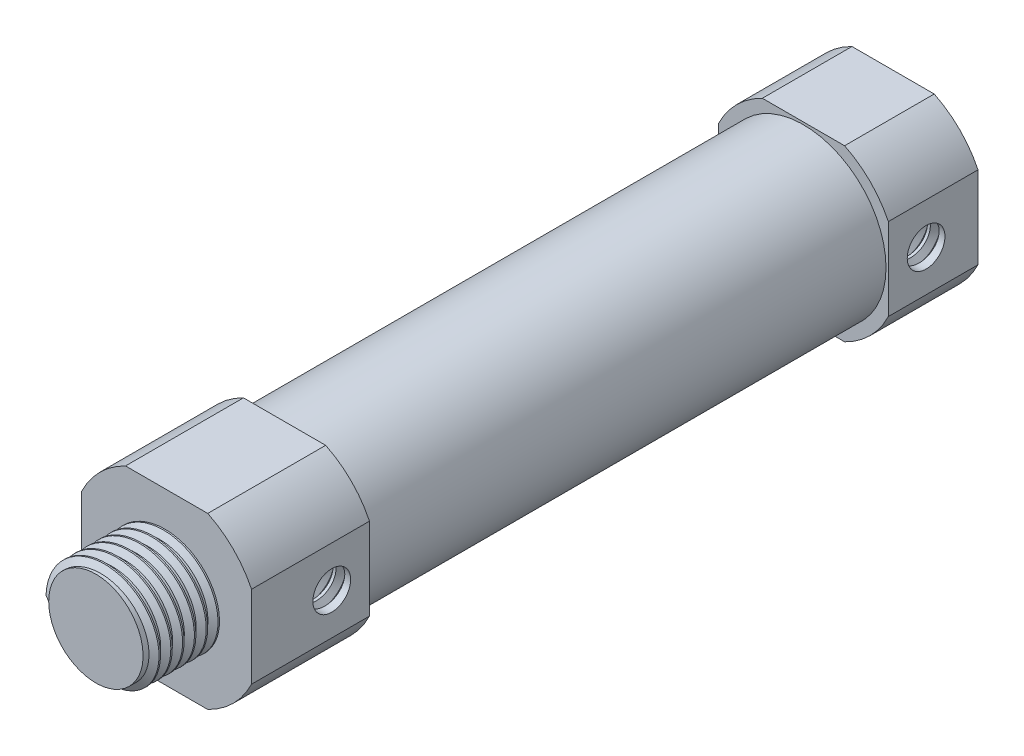
SolidWorks part; units mm, degrees
material "1060 合金"
ref_plane "前视基准面" through (0, 0, 0) normal (0, 0, 1) x (1, 0, 0)
ref_plane "上视基准面" through (0, 0, 0) normal (0, 1, 0) x (1, 0, 0)
ref_plane "右视基准面" through (0, 0, 0) normal (1, 0, 0) x (0, 0, -1)
sketch "草图1" plane through (0, 0, 0) normal (0, 0, 1) x (1, 0, 0)
  circle A0 centre (0, 0) radius 10
  dimension "D1" = 20
extrude "凸台-拉伸1" add sketch "草图1" along normal blind 9.5
sketch "草图2" plane through (0, 0, 9.5) normal (0, 0, 1) x (1, 0, 0)
  line L1 (-9, 9) -> (9, 9)
  line L2 (-9, 9) -> (-9, -9)
  line L3 (-9, -9) -> (9, -9)
  line L4 (9, 9) -> (9, -9)
  line L5 (-9, 9) -> (9, -9) construction
  line L6 (-9, -9) -> (9, 9) construction
  circle A0 centre (0, 0) radius 15
  point P0 (0, 0)
  dimension "D2" = 30
  dimension "D1" = 18
extrude "切除-拉伸1" cut sketch "草图2" against normal blind 9.5
sketch "草图3" plane through (0, 0, 9.5) normal (0, 0, 1) x (1, 0, 0)
  circle A0 centre (0, 0) radius 8.75
  dimension "D1" = 17.5
extrude "凸台-拉伸2" add sketch "草图3" along normal blind 55
sketch "草图4" plane through (0, 0, 64.5) normal (0, 0, 1) x (1, 0, 0)
  line L1 (9, -9) -> (-9, -9)
  line L2 (9, -9) -> (9, 9)
  line L3 (9, 9) -> (-9, 9)
  line L4 (-9, -9) -> (-9, 9)
  line L5 (9, -9) -> (-9, 9) construction
  line L6 (9, 9) -> (-9, -9) construction
  circle A0 centre (0, 0) radius 10
  circle M5 centre (0, 0) radius 8.75
  dimension "D1" = 20
  dimension "D2" = 18
extrude "凸台-拉伸3" add sketch "草图4" along normal blind 12.5 contours M5 | L2 A0 L3 L4 L1 M5 region at (0, -8.9745, 64.5) region at (0, 0, 64.5)
sketch "草图5" plane through (0, 0, 77) normal (0, 0, 1) x (1, 0, 0)
  circle A0 centre (0, 0) radius 5
  dimension "D1" = 10
extrude "凸台-拉伸4" add sketch "草图5" along normal blind 7.5
thread "螺纹线1" pitch 1.25 method extrude profile "螺纹线轮廓1" start angle 0, offset 0, length 7.5, pitch 1.25, diameter 10
ref_plane "基准面1" through (-5, 0, 84.5) normal (0, -1, 0) x (-1, 0, 0)
sketch "螺纹线轮廓1" plane through (-5, 0, 84.5) normal (0, -1, 0) x (-1, 0, 0)
  line L0 (0, 0) -> (0, 1.25) construction
  line L1 (0, 0) -> (0.6766, 0.3906)
  line L2 (0.6766, 0.3906) -> (0.6766, 0.5469)
  line L3 (0.6766, 0.5469) -> (0, 0.9375)
  line L4 (0.6766, 0.4687) -> (0, 0.4687) construction
  line L11 (0, 0) -> (0, 0.9375)
  point P2 (0, 0)
  dimension "Pitch" = 1.25
  dimension "Profile_Angle" = 60
  dimension "Profile_Land" = 0.1562
  dimension "Profile_Height" = 0.6766
sketch "草图11" plane through (9, 0, 0) normal (1, 0, 0) x (0, 0, -1)
  line L0 (-64.5, -4.3589) -> (-64.5, 4.3589) construction
  line L1 (-9.5, 8.75) -> (-9.5, -8.75) construction
  circle A0 centre (-68.5, 0) radius 2
  circle A1 centre (-5.5, 0) radius 2
  dimension "D1" = 4
  dimension "D2" = 4
  dimension "D3" = 4
  dimension "D4" = 4
extrude "切除-拉伸2" cut sketch "草图11" against normal blind 5
thread "螺纹线2" pitch 1.25 method cut profile "螺纹线轮廓2" start angle 0, offset 0, length 5, pitch 1.25, diameter 4
ref_plane "基准面2" through (9, 0, 70.5) normal (0, -1, 0) x (0, 0, 1)
sketch "螺纹线轮廓2" plane through (9, 0, 70.5) normal (0, -1, 0) x (0, 0, 1)
  line L0 (0, 0) -> (0, 1.25) construction
  line L1 (0, 0) -> (0.6766, 0.3906)
  line L2 (0.6766, 0.3906) -> (0.6766, 0.5469)
  line L3 (0.6766, 0.5469) -> (0, 0.9375)
  line L4 (0.6766, 0.4687) -> (0, 0.4687) construction
  line L11 (0, 0) -> (0, 0.9375)
  point P2 (0, 0)
  dimension "Pitch" = 1.25
  dimension "Profile_Angle" = 60
  dimension "Profile_Land" = 0.1562
  dimension "Profile_Height" = 0.6766
thread "螺纹线3" pitch 1.25 method cut profile "螺纹线轮廓3" start angle 0, offset 0, length 5, pitch 1.25, diameter 4
ref_plane "基准面3" through (9, 0, 7.5) normal (0, -1, 0) x (0, 0, 1)
sketch "螺纹线轮廓3" plane through (9, 0, 7.5) normal (0, -1, 0) x (0, 0, 1)
  line L0 (0, 0) -> (0, 1.25) construction
  line L1 (0, 0) -> (0.6766, 0.3906)
  line L2 (0.6766, 0.3906) -> (0.6766, 0.5469)
  line L3 (0.6766, 0.5469) -> (0, 0.9375)
  line L4 (0.6766, 0.4687) -> (0, 0.4687) construction
  line L11 (0, 0) -> (0, 0.9375)
  point P2 (0, 0)
  dimension "Pitch" = 1.25
  dimension "Profile_Angle" = 60
  dimension "Profile_Land" = 0.1562
  dimension "Profile_Height" = 0.6766
